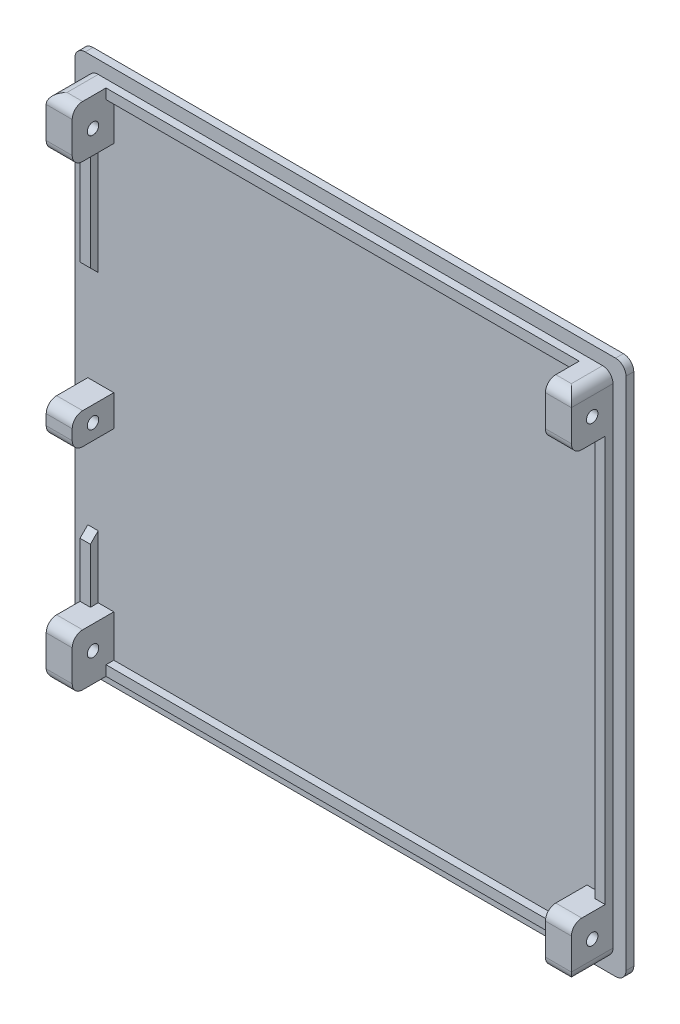
SolidWorks part; units mm, degrees
ref_plane "Спереди" through (0, 0, 0) normal (0, 0, 1) x (1, 0, 0)
ref_plane "Сверху" through (0, 0, 0) normal (0, 1, 0) x (1, 0, 0)
ref_plane "Справа" through (0, 0, 0) normal (1, 0, 0) x (0, 0, -1)
other "Configuration Table"
sketch "Эскиз1" plane through (0, 0, 0) normal (0, 0, 1) x (1, 0, 0)
  line L1 (-53, -51.5) -> (53, -51.5)
  line L2 (-53, -51.5) -> (-53, 51.5)
  line L3 (-53, 51.5) -> (53, 51.5)
  line L4 (53, -51.5) -> (53, 51.5)
  line L5 (-53, -51.5) -> (53, 51.5) construction
  line L6 (-53, 51.5) -> (53, -51.5) construction
  point P0 (0, 0)
  dimension "D1" = 103
  dimension "D2" = 106
extrude "Бобышка-Вытянуть1" add sketch "Эскиз1" along normal blind 1.5
sketch "Эскиз2" plane through (0, 0, 1.5) normal (0, 0, 1) x (1, 0, 0)
  line L0 (-53, 51.5) -> (-53, -51.5) construction
  line L1 (-50.5, -49) -> (50.5, -49)
  line L2 (-50.5, -49) -> (-50.5, 49)
  line L3 (-50.5, 49) -> (50.5, 49)
  line L4 (50.5, -49) -> (50.5, 49)
  line L5 (-50.5, -49) -> (50.5, 49) construction
  line L6 (-50.5, 49) -> (50.5, -49) construction
  line L7 (-48.5, -47.0594) -> (48.5, -47.0594)
  line L8 (-48.5, -47.0594) -> (-48.5, 47.0594)
  line L9 (-48.5, 47.0594) -> (48.5, 47.0594)
  line L10 (48.5, -47.0594) -> (48.5, 47.0594)
  line L11 (-48.5, -47.0594) -> (48.5, 47.0594) construction
  line L12 (-48.5, 47.0594) -> (48.5, -47.0594) construction
  line L13 (-53, -51.5) -> (53, -51.5) construction
  point P0 (0, 0)
  point P6 (0, 0)
  dimension "D1" = 2.5
  dimension "D2" = 2.5
  dimension "D3" = 2
extrude "Бобышка-Вытянуть2" add sketch "Эскиз2" along normal blind 1.5
sketch "Эскиз3" plane through (0, 0, 1.5) normal (0, 0, 1) x (1, 0, 0)
  line L0 (-50.5, 49) -> (-50.5, -49) construction
  line L1 (-50.5, 49) -> (-45.5, 49)
  line L2 (-50.5, 49) -> (-50.5, 39)
  line L3 (-50.5, 39) -> (-45.5, 39)
  line L4 (-45.5, 49) -> (-45.5, 39)
  line L6 (50.5, 49) -> (-50.5, 49) construction
  line L7 (-48.5, 0) -> (48.5, 0) construction
  line L8 (-48.5, 47.0594) -> (-48.5, -47.0594) construction
  line L9 (48.5, -47.0594) -> (48.5, 47.0594) construction
  line L10 (0, 47.0594) -> (0, -49) construction
  line L11 (48.5, 47.0594) -> (-48.5, 47.0594) construction
  line L12 (-50.5, -49) -> (50.5, -49) construction
  line L13 (45.5, 49) -> (45.5, 39)
  line L14 (50.5, 39) -> (45.5, 39)
  line L15 (50.5, 49) -> (50.5, 39)
  line L16 (50.5, 49) -> (45.5, 49)
  line L17 (50.5, -49) -> (45.5, -49)
  line L18 (50.5, -49) -> (50.5, -39)
  line L19 (50.5, -39) -> (45.5, -39)
  line L20 (45.5, -49) -> (45.5, -39)
  line L21 (-45.5, -49) -> (-45.5, -39)
  line L22 (-50.5, -39) -> (-45.5, -39)
  line L23 (-50.5, -49) -> (-50.5, -39)
  line L24 (-50.5, -49) -> (-45.5, -49)
  dimension "D1" = 5
  dimension "D2" = 10
extrude "Бобышка-Вытянуть3" add sketch "Эскиз3" along normal blind 8
sketch "Эскиз4" plane through (-50.5, 0, 0) normal (-1, 0, 0) x (0, 0, 1)
  line L0 (1.5, 51.5) -> (0, 51.5) construction
  line L1 (1.5, 49) -> (1.5, -49) construction
  line L2 (0, 0) -> (3, 0) construction
  line L3 (3, 39) -> (3, -39) construction
  circle A0 centre (5.5, 43.5) radius 1.1
  circle A1 centre (5.5, -43.5) radius 1.1
  dimension "D3" = 2.2
  dimension "D1" = 8
  dimension "D2" = 4
extrude "Вырез-Вытянуть1" cut sketch "Эскиз4" against normal through all
sketch "Эскиз8" plane through (0, 0, 1.5) normal (0, 0, 1) x (1, 0, 0)
  line L1 (-50.5, -2.5) -> (-45.5, -2.5)
  line L2 (-50.5, -2.5) -> (-50.5, -8.5)
  line L3 (-50.5, -8.5) -> (-45.5, -8.5)
  line L4 (-45.5, -2.5) -> (-45.5, -8.5)
  line L5 (-45.5, 39) -> (-45.5, 49) construction
  line L6 (-53, -51.5) -> (53, -51.5) construction
  line L7 (-50.5, 39) -> (-50.5, -39) construction
  dimension "D1" = 6
  dimension "D2" = 43
extrude "Бобышка-Вытянуть4" add sketch "Эскиз8" along normal up to surface (8 mm away) up to face at (-48, 44, 9.5)
fillet "Скругление1" radius 2 18 edges at (48, 49, 9.5) (48, 39, 9.5) (48, -49, 9.5) (48, -39, 9.5) (-48, -39, 9.5) (-48, -49, 9.5) (-48, 39, 9.5) (-48, 49, 9.5) (-50.5, 49, 5.5) (50.5, 49, 5.5) (50.5, -49, 5.5) (-50.5, -49, 5.5) (-53, -51.5, 0.75) (53, -51.5, 0.75) (53, 51.5, 0.75) (-53, 51.5, 0.75) (-48, -2.5, 9.5) (-48, -8.5, 9.5)
sketch "Эскиз5" plane through (0, 0, 0) normal (0, 0, -1) x (-1, 0, 0)
  text T0 "<b>   KENOBI-S1</b>\r\n<b>OnStep v_4.24</b>" font "Arial" height 8
extrude "Вырез-Вытянуть2" cut sketch "Эскиз5" against normal blind 0.6
sketch "Эскиз6" plane through (0, 0, 0) normal (0, 0, -1) x (-1, 0, 0)
  line L0 (51, -24.5) -> (46, -24.5)
  line L1 (46, -24.5) -> (46, -12.5)
  line L2 (46, -12.5) -> (51, -12.5)
  line L3 (51, -12.5) -> (51, -13.5)
  line L4 (51, -13.5) -> (47, -13.5)
  line L5 (47, -13.5) -> (47, -23.5)
  line L6 (47, -23.5) -> (51, -23.5)
  line L7 (51, -23.5) -> (51, -24.5)
  line L8 (51, -51.5) -> (-51, -51.5) construction
  line L9 (53, 49.5) -> (53, -49.5) construction
  line L10 (51, 1.5) -> (46, 1.5)
  line L11 (46, 1.5) -> (46, 13.5)
  line L12 (46, 13.5) -> (51, 13.5)
  line L13 (51, 13.5) -> (51, 12.5)
  line L14 (51, 12.5) -> (47, 12.5)
  line L15 (47, 12.5) -> (47, 2.5)
  line L16 (47, 2.5) -> (51, 2.5)
  line L17 (51, 2.5) -> (51, 1.5)
  dimension "D1" = 1
  dimension "D2" = 1
  dimension "D3" = 10
  dimension "D4" = 5
  dimension "D5" = 27
  dimension "D6" = 2
  dimension "D7" = 2
extrude "Вырез-Вытянуть3" cut sketch "Эскиз6" against normal blind 0.6
sketch "Эскиз7" plane through (0, 0, 0) normal (0, 0, -1) x (-1, 0, 0)
  line L0 (45, -11.4818) -> (45, -27.4121) construction
  line L1 (45, 2.2558) -> (45, 13.4419) construction
  line L2 (46, -12.5) -> (46, -24.5) construction
  text T0 "<b>RA</b>" font "Arial" height 5
  text T1 "<b>DEC</b>" font "Arial" height 5
  dimension "D1" = 1
extrude "Вырез-Вытянуть4" cut sketch "Эскиз7" against normal blind 0.6
sketch "Эскиз9" plane through (-50.5, 0, 0) normal (-1, 0, 0) x (0, 0, 1)
  line L0 (9.5, -4.5) -> (9.5, -6.5) construction
  line L1 (5.5, 43.5) -> (5.5, -5.5) construction
  circle A0 centre (5.5, -5.5) radius 1.1
  point P4 (9.5, -5.5)
  dimension "D1" = 2.2
extrude "Вырез-Вытянуть5" cut sketch "Эскиз9" against normal up to surface (5 mm away) up to face at (-45.5, -5.5, 6.3047)
ref_axis "Ось1" through (-45.5, -5.5, 5.5) along (-1, 0, 0)
sketch "Эскиз10" plane through (0, 0, 1.5) normal (0, 0, 1) x (1, 0, 0)
  line L0 (-48.5, 39) -> (-48.5, -2.5) construction
  line L1 (-50.5, -2.5) -> (-48.5, -2.5)
  line L2 (-50.5, -2.5) -> (-50.5, 15.5)
  line L3 (-50.5, 15.5) -> (-48.5, 15.5)
  line L4 (-48.5, -2.5) -> (-48.5, 15.5)
  line L5 (-48.5, -8.5) -> (-48.5, -39) construction
  line L6 (-50.5, -8.5) -> (-48.5, -8.5)
  line L7 (-50.5, -8.5) -> (-50.5, -26.5)
  line L8 (-50.5, -26.5) -> (-48.5, -26.5)
  line L9 (-48.5, -8.5) -> (-48.5, -26.5)
  dimension "D1" = 18
extrude "Вырез-Вытянуть6" cut sketch "Эскиз10" along normal up to surface (1.5 mm away) up to face at (-49.5, 18.25, 3)
chamfer "Фаска1" distance 2 angle 45 2 edges at (-49.5, -26.5, 3) (-49.5, 15.5, 3)
